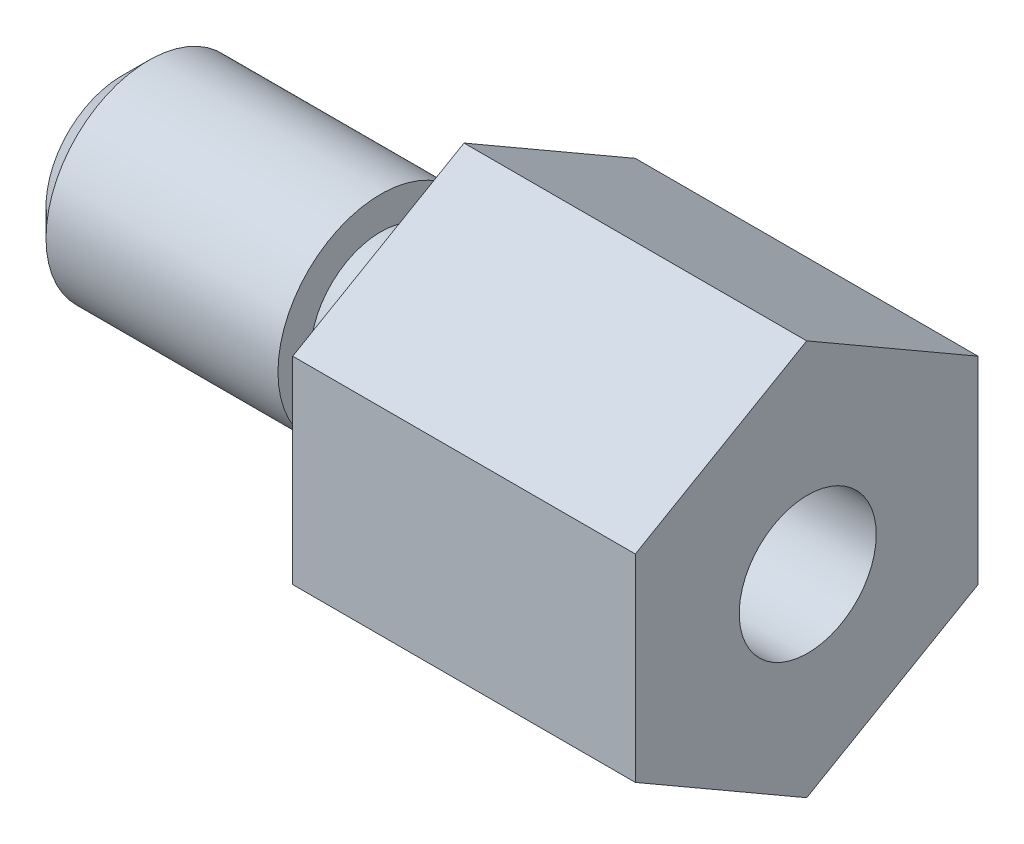
SolidWorks part; units mm, degrees
material "Laiton"
ref_plane "Front Plane" through (0, 0, 0) normal (0, 0, 1) x (1, 0, 0)
ref_plane "Top Plane" through (0, 0, 0) normal (0, 1, 0) x (1, 0, 0)
ref_plane "Right Plane" through (0, 0, 0) normal (1, 0, 0) x (0, 0, -1)
ref_plane "Plan1" through (0, 0, 0) normal (-1, 0, 0) x (0, -1, 0)
sketch "Esquisse1" plane through (0, 0, 0) normal (-1, 0, 0) x (0, -1, 0)
  line L0 (-1.4434, -2.5) -> (1.4434, -2.5)
  line L1 (1.4434, -2.5) -> (2.8868, 0)
  line L2 (2.8868, 0) -> (1.4434, 2.5)
  line L3 (1.4434, 2.5) -> (-1.4434, 2.5)
  line L4 (-1.4434, 2.5) -> (-2.8868, 0)
  line L5 (-2.8868, 0) -> (-1.4434, -2.5)
  dimension "D1" = 5
extrude "Boss.-Extru.1" add sketch "Esquisse1" against normal blind 5
ref_plane "Plan2" through (0, 0, 0) normal (0, 0, -1) x (-1, 0, 0)
sketch "Esquisse2" plane through (0, 0, 0) normal (0, 0, -1) x (-1, 0, 0)
  line L0 (0, 1.1577) -> (0, 0.1333)
  line L1 (0, 0.1333) -> (5, 0.1333)
  line L2 (5, 0.1333) -> (5, 1.6333)
  line L3 (5, 1.6333) -> (1.2154, 1.6333)
  line L4 (1.2154, 1.6333) -> (1.2154, 1.1577)
  line L5 (1.2154, 1.1577) -> (0, 1.1577)
  line L6 (0, 0.1333) -> (5, 0.1333) construction
  dimension "D1" = 1.5
  dimension "D2" = 5
revolve "Révolution1" add sketch "Esquisse2" angle 360 about L6 reverse direction yes
hole_wizard "Diamètre du perçage Ø2.0 (2)1" positions "Esquisse4" profile "Esquisse3" hole size "Ø2.0" standard "Ansi Metric"
sketch "Esquisse4" plane through (5, 0, 0) normal (1, 0, 0) x (0, 0, -1)
  point P0 (0.0152, -0.0683)
sketch "Esquisse3" plane through (5, -0.0683, -0.0152) normal (0, 1, 0) x (0, 0, -1)
  line L0 (0, 0) -> (0, 10.6009)
  line L1 (0, 10.6009) -> (1, 10)
  line L2 (1, 10) -> (1, 0)
  line L5 (1, 0) -> (0, 0)
  line L10 (0, 10.6009) -> (-1, 10) construction
  line L11 (0, -6.35) -> (0, 107.95) construction
  dimension "Diamètre du perçage" = 2
  dimension "Profondeur du perçage" = 10
  dimension "Angle de pointe" = 118
chamfer "Chanfrein1" distance 0.4 angle 45 1 edges at (-5, 0.1333, 1.5)
